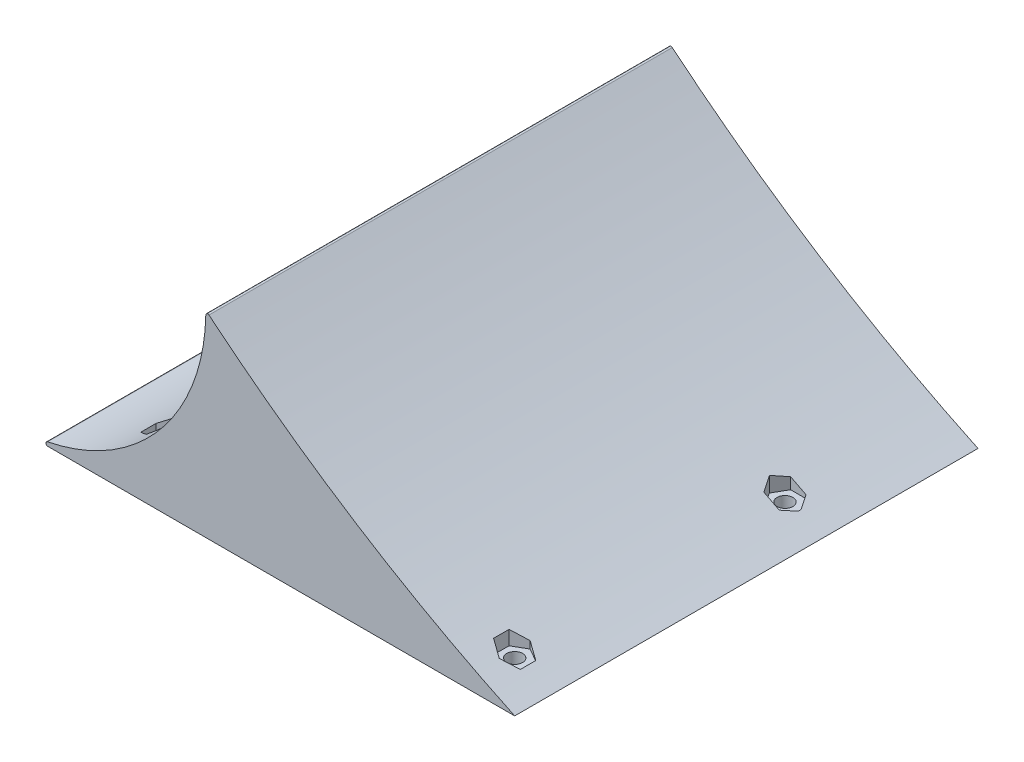
SolidWorks part; units mm, degrees
ref_plane "前视基准面" through (0, 0, 0) normal (0, 0, 1) x (1, 0, 0)
ref_plane "上视基准面" through (0, 0, 0) normal (0, 1, 0) x (1, 0, 0)
ref_plane "右视基准面" through (0, 0, 0) normal (1, 0, 0) x (0, 0, -1)
sketch "草图2" plane through (0, 0, 0) normal (0, 0, 1) x (1, 0, 0)
  circle A1 centre (0, 0) radius 33.5
  dimension "D3" = 67
sketch "草图3" plane through (0, 0, 0) normal (0, 0, 1) x (1, 0, 0)
  line L0 (0, 0) -> (0, -51) construction
  line L1 (0, -51) -> (131, -51) construction
  line L2 (131, -51) -> (0, -51)
  arc A0 (51, 0) -> (131, -51) centre (291.4441, 288.9221) ccw
  circle A1 centre (0, 0) radius 33.5 construction
  circle A2 centre (0, 0) radius 34.5
  arc A3 (0, -51) -> (51, 0) centre (0, 0) ccw
  dimension "D3" = 1
  dimension "D4" = 51
  dimension "D2" = 131
extrude "凸台-拉伸1" add sketch "草图3" along normal mid plane 240 contours A3 L2 A0 A2 region at (67.8421, -35.8914, 0)
fillet "圆角1" radius 0.5 2 edges at (0, -51, 0) (51, 0, 0)
sketch "草图4" plane through (0, 0, 0) normal (0, 1, 0) x (1, 0, 0)
  line L0 (51.8079, -120) -> (131, -120) construction
  line L1 (124.4641, -112) -> (124.4641, -108)
  line L2 (124.4641, -108) -> (121, -106)
  line L3 (121, -106) -> (117.5359, -108)
  line L4 (117.5359, -108) -> (117.5359, -112)
  line L5 (117.5359, -112) -> (121, -114)
  line L6 (121, -114) -> (124.4641, -112)
  line L7 (29.5995, -106) -> (26.1354, -108)
  line L8 (26.1354, -108) -> (26.1354, -112)
  line L9 (26.1354, -112) -> (29.5995, -114)
  line L10 (29.5995, -114) -> (33.0636, -112)
  line L11 (33.0636, -112) -> (33.0636, -108)
  line L12 (33.0636, -108) -> (29.5995, -106)
  line L13 (131, -120) -> (131, 120) construction
  line L14 (10.0015, -120) -> (50.9893, -120) construction
  line L15 (121, -110) -> (121, 110) construction
  line L16 (9.5995, 120) -> (9.5995, -120) construction
  line L17 (0, 0) -> (131, 0) construction
  line L18 (-33.5, 0) -> (33.5, 0) construction
  line L19 (33.0636, 108) -> (29.5995, 106)
  line L20 (33.0636, 112) -> (33.0636, 108)
  line L21 (29.5995, 114) -> (33.0636, 112)
  line L22 (26.1354, 112) -> (29.5995, 114)
  line L23 (26.1354, 108) -> (26.1354, 112)
  line L24 (29.5995, 106) -> (26.1354, 108)
  line L25 (121, 114) -> (124.4641, 112)
  line L26 (117.5359, 112) -> (121, 114)
  line L27 (117.5359, 108) -> (117.5359, 112)
  line L28 (121, 106) -> (117.5359, 108)
  line L29 (124.4641, 108) -> (121, 106)
  line L30 (124.4641, 112) -> (124.4641, 108)
  line L31 (29.5995, -110) -> (121, -110) construction
  line L32 (123, -36.5359) -> (119, -36.5359)
  line L33 (119, -36.5359) -> (117, -40)
  line L34 (117, -40) -> (119, -43.4641)
  line L35 (119, -43.4641) -> (123, -43.4641)
  line L36 (123, -43.4641) -> (125, -40)
  line L37 (125, -40) -> (123, -36.5359)
  line L38 (125, 40) -> (123, 43.4641)
  line L39 (123, 43.4641) -> (119, 43.4641)
  line L40 (119, 43.4641) -> (117, 40)
  line L41 (117, 40) -> (119, 36.5359)
  line L42 (119, 36.5359) -> (123, 36.5359)
  line L43 (123, 36.5359) -> (125, 40)
  line L44 (121, -110) -> (124.4641, -109.585) construction
  circle A0 centre (121, -110) radius 3.4641 construction
  circle A1 centre (29.5995, -110) radius 3.4641 construction
  circle A2 centre (29.5995, 110) radius 3.4641 construction
  circle A3 centre (121, 110) radius 3.4641 construction
  circle A4 centre (121, -40) radius 3.4641 construction
  circle A5 centre (121, 40) radius 3.4641 construction
  dimension "D1" = 4
  dimension "D2" = 10
  dimension "D3" = 10
  dimension "D4" = 10
  dimension "D5" = 20
  dimension "D6" = 80
extrude "切除-拉伸1" cut sketch "草图4" against normal offset from surface (48 mm away) 3 up to face at (70.5498, -51, 0)
sketch "草图5" plane through (0, -48, 0) normal (0, 1, 0) x (1, 0, 0)
  line L0 (33.0636, -110) -> (26.1354, -110) construction
  line L1 (33.0636, -112) -> (33.0636, -108) construction
  line L2 (26.1354, -108) -> (26.1354, -112) construction
  line L3 (31.3316, -107) -> (27.8675, -113) construction
  line L6 (33.0636, -108) -> (29.5995, -106) construction
  line L7 (29.5995, -114) -> (26.1354, -112) construction
  line L8 (26.1354, -110) -> (33.0636, -110) construction
  line L10 (75.2998, 0) -> (0, 0) construction
  line L14 (75.2998, -110) -> (33.0636, -110) construction
  line L17 (75.2998, -110) -> (75.2998, 110) construction
  line L18 (26.1354, 110) -> (124.4641, 110) construction
  line L21 (-33.5, 0) -> (33.5, 0) construction
  line L22 (26.1354, 112) -> (26.1354, 108) construction
  line L24 (124.4641, 108) -> (124.4641, 112) construction
  line L25 (118, 38.2679) -> (123.8961, 41.912) construction
  line L26 (119, 36.5359) -> (117, 40) construction
  line L27 (124.7922, 40.3598) -> (123, 43.4641) construction
  line L28 (121, -36.5359) -> (121, -43.4641) construction
  line L29 (123, -36.5359) -> (119, -36.5359) construction
  line L30 (123, -43.4641) -> (119, -43.4641) construction
  circle A0 centre (29.5995, -110) radius 2.05
  circle A2 centre (29.5995, 110) radius 2.05
  circle A6 centre (121, 110) radius 2.05
  circle A7 centre (121, -110) radius 2.05
  circle A8 centre (120.9481, 40.09) radius 2.05
  circle A9 centre (121, -40) radius 2.05
  point P17 (75.2998, 110)
  dimension "D1" = 4.1
extrude "切除-拉伸2" cut sketch "草图5" against normal blind 5 contours A0 | A8 | A2 | A7 | A9 | A6 region at (29.5995, -48, 110) region at (120.9481, -48, -40.09)
sketch "草图6" plane through (0, 0, 0) normal (0, 0, 1) x (1, 0, 0)
  line L0 (131, -51) -> (10.0995, -51) construction
  circle A0 centre (70.5498, -51) radius 70.9969
extrude "切除-拉伸3" cut sketch "草图6" against normal through all
